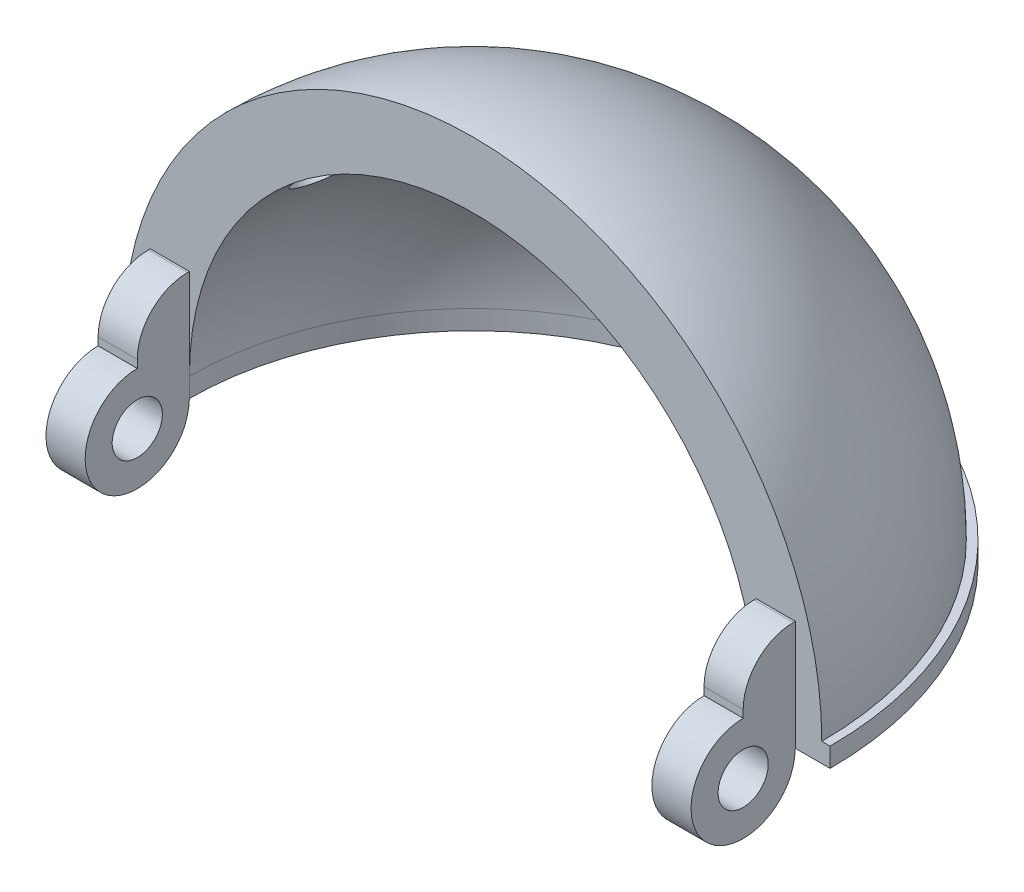
SolidWorks part; units mm, degrees
ref_plane "Front Plane" through (0, 0, 0) normal (0, 0, 1) x (1, 0, 0)
ref_plane "Top Plane" through (0, 0, 0) normal (0, 1, 0) x (1, 0, 0)
ref_plane "Right Plane" through (0, 0, 0) normal (1, 0, 0) x (0, 0, -1)
sketch "Sketch1" plane through (0, 0, 0) normal (0, 1, 0) x (1, 0, 0)
  line L2 (-18.4463, 0) -> (28.559, 0) construction
  line L4 (-18.4463, 0) -> (-13.5837, 0)
  line L8 (23.6964, 0) -> (28.559, 0)
  arc A0 (-18.4463, 0) -> (28.559, 0) centre (5.0564, 0) cw
  arc A1 (-13.5837, 0) -> (23.6964, 0) centre (5.0564, 0) cw
extrude "Boss-Extrude1" add sketch "Sketch1" along normal blind 1.27
sketch "Sketch4" plane through (0, 1.27, 0) normal (0, 1, 0) x (1, 0, 0)
  line L0 (-18.4463, 0) -> (-13.5837, 0) construction
  line L1 (23.6964, 0) -> (28.559, 0) construction
  line L2 (23.6964, 0) -> (28.0144, 0)
  line L3 (-17.9017, 0) -> (-13.5837, 0)
  line L4 (-17.9017, 0) -> (28.0144, 0) construction
  arc A0 (-13.5837, 0) -> (23.6964, 0) centre (5.0564, 0) cw
  arc A1 (-17.9017, 0) -> (28.0144, 0) centre (5.0564, 0) cw
  dimension "D1" = 4.318
  dimension "D2" = 4.318
revolve "Revolve3" add sketch "Sketch4" angle 90 about L4
sketch "Sketch6" plane through (0, 0, 0) normal (0, 0, 1) x (1, 0, 0)
  line L1 (23.6964, 0) -> (28.559, 0)
  line L2 (23.6964, 0) -> (23.6964, 1.27)
  line L3 (23.6964, 1.27) -> (28.559, 1.27)
  line L4 (28.559, 0) -> (28.559, 1.27)
  line L5 (-18.4463, 1.27) -> (-13.5837, 1.27)
  line L6 (-18.4463, 1.27) -> (-18.4463, 0)
  line L7 (-18.4463, 0) -> (-13.5837, 0)
  line L8 (-13.5837, 1.27) -> (-13.5837, 0)
extrude "Boss-Extrude3" add sketch "Sketch6" along normal blind 7.9355 contours L8 L5 L6 L7 | L3 L4 L1 L2 region at (-16.015, 0.635, 0)
sketch "Sketch10" plane through (0, 1.27, 0) normal (0, 1, 0) x (1, 0, 0)
  line L1 (-18.4463, -7.9355) -> (-13.5837, -7.9355)
  line L2 (-18.4463, -7.9355) -> (-18.4463, 0)
  line L3 (-18.4463, 0) -> (-13.5837, 0)
  line L4 (-13.5837, -7.9355) -> (-13.5837, 0)
  line L5 (23.6964, 0) -> (28.559, 0)
  line L6 (23.6964, 0) -> (23.6964, -7.9355)
  line L7 (23.6964, -7.9355) -> (28.559, -7.9355)
  line L8 (28.559, 0) -> (28.559, -7.9355)
extrude "Boss-Extrude4" add sketch "Sketch10" along normal blind 3.81 and the other way blind 6.35
fillet "Fillet7" radius 5.08 1 edges at (-16.015, 5.08, 7.9355) type face fillet first side face at (-16.015, 0, 7.9355) second side face at (-16.3286, 5.08, 3.1742)
fillet "Fillet10" radius 5.08 1 edges at (26.1277, 5.08, 7.9355) type face fillet first side face at (26.4413, 5.08, 3.1742) second side face at (26.1277, 0, 7.9355)
sketch "Sketch13" plane through (-18.4463, 0, 0) normal (-1, 0, 0) x (0, 0, 1)
  line L1 (0, 5.08) -> (2.8555, 5.08) construction
  circle A0 centre (3.4286, 0) radius 1.651
  dimension "D1" = 3.302
  dimension "D2" = 5.08
extrude "Cut-Extrude2" cut sketch "Sketch13" against normal blind 55.372
sketch "Sketch14" plane through (0, 5.08, 0) normal (0, 1, 0) x (1, 0, 0)
  line L1 (28.559, 0) -> (26.273, 0)
  line L2 (28.559, 0) -> (28.559, -11.3681)
  line L3 (28.559, -11.3681) -> (26.273, -11.3681)
  line L4 (26.273, 0) -> (26.273, -11.3681)
  line L5 (-18.4463, 0) -> (-16.1603, 0)
  line L6 (-18.4463, 0) -> (-18.4463, -11.3681)
  line L7 (-18.4463, -11.3681) -> (-16.1603, -11.3681)
  line L8 (-16.1603, 0) -> (-16.1603, -11.3681)
  dimension "D1" = 2.286
  dimension "D2" = 2.286
extrude "Cut-Extrude3" cut sketch "Sketch14" against normal blind 55.372
fillet "Fillet15" 2 edges at (24.9847, -5.08, 7.9355) (24.9847, -5.08, 0) type full round first side face at (24.9847, -2.54, 7.9355) second side face at (24.9847, -2.54, 0) middle face at (24.9847, -5.08, 3.9678)
fillet "Fillet16" 2 edges at (-14.872, -5.08, 0) (-14.872, -5.08, 7.9355) type full round first side face at (-14.872, -2.54, 0) second side face at (-14.872, -2.54, 7.9355) middle face at (-14.872, -5.08, 3.9678)
sketch "Sketch16" plane through (26.273, 0, 0) normal (1, 0, 0) x (0, 0, -1)
  line L0 (-7.9355, -1.1122) -> (-7.9355, 0) construction
  arc A1 (0, 0) -> (-7.9355, -0.5561) centre (-3.9961, 0.1259) cw
  arc A2 (0, 0) -> (-7.9355, -0.5561) centre (-3.9138, -1.048) cw
extrude "Cut-Extrude4" cut sketch "Sketch16" against normal blind 55.372 body kept at (-13.5837, 0, 7.9355)
sketch "Sketch18" plane through (26.273, 0, 0) normal (1, 0, 0) x (0, 0, -1)
  line L0 (-3.4286, 3.4286) -> (0, 3.4286)
  line L1 (0, 3.4286) -> (0, 5.4674)
  line L2 (0, 5.4674) -> (-9.0316, 5.4674)
  line L3 (-9.0316, 5.4674) -> (-9.0316, -4.4868)
  line L4 (-9.0316, -4.4868) -> (0, -4.4868)
  line L5 (0, -4.4868) -> (0, 0)
  arc A0 (-3.4286, 3.4286) -> (0, 0) centre (-3.4286, 0) ccw
extrude "Cut-Extrude7" cut sketch "Sketch18" against normal blind 55.88
sketch "Sketch19" plane through (0, 3.4286, 0) normal (0, 1, 0) x (1, 0, 0)
  line L1 (23.6964, 0) -> (26.273, 0)
  line L2 (23.6964, 0) -> (23.6964, -3.4286)
  line L3 (23.6964, -3.4286) -> (26.273, -3.4286)
  line L4 (26.273, 0) -> (26.273, -3.4286)
  line L5 (-16.1603, 0) -> (-13.5837, 0)
  line L6 (-16.1603, 0) -> (-16.1603, -3.4286)
  line L7 (-16.1603, -3.4286) -> (-13.5837, -3.4286)
  line L8 (-13.5837, 0) -> (-13.5837, -3.4286)
extrude "Boss-Extrude5" add sketch "Sketch19" along normal blind 3.81
fillet "Fillet17" radius 3.302 1 edges at (24.9847, 7.2386, 3.4286) type face fillet first side face at (24.9847, 7.2386, 1.7143) second side face at (24.9847, 5.3336, 3.4286)
fillet "Fillet18" radius 3.302 1 edges at (-14.872, 7.2386, 3.4286) type face fillet first side face at (-14.872, 5.3336, 3.4286) second side face at (-14.872, 7.2386, 1.7143)
hole_wizard "#96 (0.0063) Diameter Hole2" positions "3DSketch2" profile "Sketch21" hole size "#96" standard "ANSI Inch"
sketch3d "3DSketch2"
  point P0 (-11.5296, 16.5481, -4.3075)
sketch "Sketch21" plane through (-11.5296, 16.5481, -4.3075) normal (0.4237, 0.6405, 0.6405) x (-0.5464, -0.3832, 0.7447)
  line L0 (0, 0) -> (0, 26.392)
  line L1 (0, 26.392) -> (1.651, 25.4)
  line L2 (1.651, 25.4) -> (1.651, 0)
  line L5 (1.651, 0) -> (0, 0)
  line L10 (0, 26.392) -> (-1.651, 25.4) construction
  line L11 (0, -6.35) -> (0, 107.95) construction
  dimension "Hole Dia." = 3.302
  dimension "Hole Depth" = 25.4
  dimension "Drill Angle" = 118
